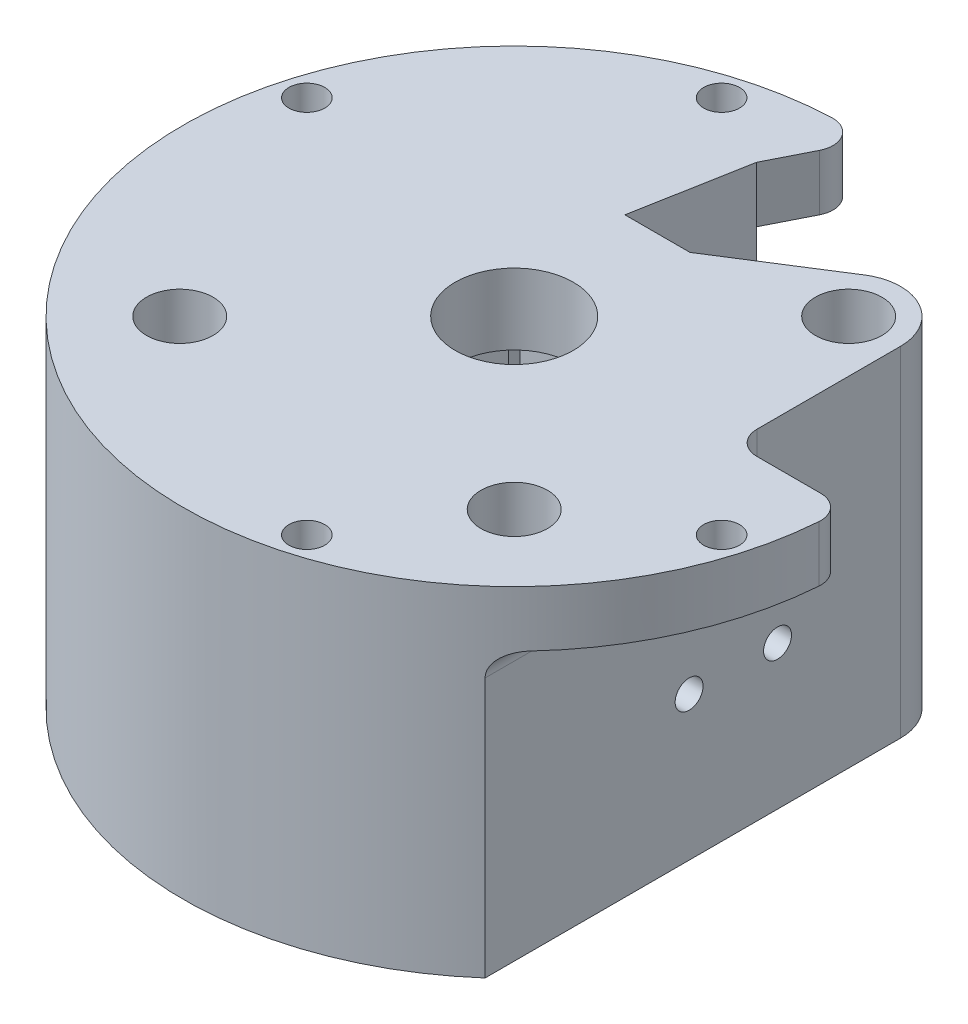
SolidWorks part; units mm, degrees
ref_plane "Front Plane" through (0, 0, 0) normal (0, 0, 1) x (1, 0, 0)
ref_plane "Top Plane" through (0, 0, 0) normal (0, 1, 0) x (1, 0, 0)
ref_plane "Right Plane" through (0, 0, 0) normal (1, 0, 0) x (0, 0, -1)
sketch "Sketch2" plane through (0, 0, 0) normal (0, 1, 0) x (1, 0, 0)
  line L0 (-46.3406, 15.0473) -> (-20.9548, -39.0545) construction
  line L1 (-17.9605, 17.9605) -> (-3.0236, 17.9605) construction
  line L2 (-17.9605, 17.9605) -> (-17.9605, -17.9605) construction
  line L3 (-17.9605, -17.9605) -> (17.9605, -17.9605) construction
  line L4 (17.9605, 17.9605) -> (17.9605, -17.9605) construction
  line L5 (-17.9605, 17.9605) -> (17.9605, -17.9605) construction
  line L6 (-17.9605, -17.9605) -> (17.9605, 17.9605) construction
  line L7 (10.05, -30.05) -> (-10.05, -30.05)
  line L8 (10.05, -30.05) -> (10.05, 10.05)
  line L9 (10.05, 10.05) -> (3.4925, 10.05)
  line L10 (-10.05, -30.05) -> (-10.05, 10.05)
  line L11 (10.05, -30.05) -> (-10.05, 10.05) construction
  line L12 (10.05, 10.05) -> (-10.05, -30.05) construction
  line L13 (-3.4925, 15.384) -> (3.4925, 15.384) construction
  line L14 (-3.4925, 15.384) -> (-3.4925, 10.05)
  line L15 (0, 10.05) -> (3.4925, 10.05) construction
  line L16 (3.4925, 15.384) -> (3.4925, 10.05)
  line L17 (0, 12.717) -> (3.4925, 10.05) construction
  line L18 (0, 12.717) -> (3.4925, 15.384) construction
  line L19 (-1.3182, 27.3309) -> (-10.8398, 32.142)
  line L20 (-1.3182, 27.3309) -> (-23.3118, -16.1961) construction
  line L21 (-23.3118, -16.1961) -> (-32.8333, -11.3851) construction
  line L22 (-10.8398, 32.142) -> (-32.8333, -11.3851) construction
  line L23 (-1.3182, 27.3309) -> (-32.8333, -11.3851) construction
  line L24 (-23.3118, -16.1961) -> (-10.8398, 32.142) construction
  line L25 (23.5324, -17.9605) -> (23.5324, -26.6597)
  line L26 (23.5324, -17.9605) -> (23.5324, 17.9605)
  line L27 (3.4925, 15.384) -> (14.9767, 22.6661)
  line L28 (-10.8398, 32.142) -> (-12.8493, 33.1573)
  line L29 (-3.4925, 15.384) -> (-1.3182, 27.3309)
  line L30 (-3.0236, 17.9605) -> (7.5558, 17.9605) construction
  line L31 (7.5558, 17.9605) -> (17.9605, 17.9605) construction
  line L32 (-3.4925, 15.384) -> (0, 12.717) construction
  line L33 (-3.4925, 10.05) -> (0, 12.717) construction
  line L34 (0, 10.05) -> (-3.4925, 10.05) construction
  line L35 (-3.4925, 10.05) -> (-10.05, 10.05)
  line L36 (-3.4925, 10.05) -> (0, 10.05) construction
  line L37 (3.4925, 10.05) -> (0, 10.05) construction
  arc A0 (-12.8493, 33.1573) -> (23.5324, -26.6597) centre (0, 0) ccw
  circle A1 centre (-17.9605, 17.9605) radius 3.5719 construction
  circle A2 centre (17.9605, 17.9605) radius 3.5719
  circle A3 centre (17.9605, -17.9605) radius 3.5719
  circle A4 centre (-17.9605, -17.9605) radius 3.5719
  arc A5 (-4.4901, 4.4901) -> (4.4901, 4.4901) centre (0, 0) ccw construction
  arc A6 (-7.1064, 7.1064) -> (7.1064, 7.1064) centre (0, 0) ccw construction
  circle A7 centre (-17.9605, -17.9605) radius 5.5719 construction
  arc A8 (23.5324, -17.9605) -> (17.9605, -12.3886) centre (17.9605, -17.9605) ccw construction
  arc A9 (23.5324, 17.9605) -> (14.9767, 22.6661) centre (17.9605, 17.9605) ccw
  arc A10 (23.5324, -26.6597) -> (-12.8493, 33.1573) centre (0, 0) ccw construction
  arc A11 (0, 10.05) -> (-7.1064, 7.1064) centre (0, 0) ccw construction
  arc A12 (4.4901, 4.4901) -> (-4.4901, 4.4901) centre (0, 0) ccw construction
  arc A13 (7.1064, 7.1064) -> (0, 10.05) centre (0, 0) ccw construction
  arc A14 (14.0206, 14.0206) -> (17.9605, 12.3886) centre (17.9605, 17.9605) ccw construction
  arc A15 (12.3886, 17.9605) -> (14.0206, 14.0206) centre (17.9605, 17.9605) ccw construction
  arc A16 (14.9767, 22.6661) -> (12.3886, 17.9605) centre (17.9605, 17.9605) ccw construction
  arc A17 (17.9605, 12.3886) -> (23.5324, 17.9605) centre (17.9605, 17.9605) ccw construction
  arc A18 (12.3886, -17.9605) -> (23.5324, -17.9605) centre (17.9605, -17.9605) ccw construction
  arc A19 (14.0206, -14.0206) -> (12.3886, -17.9605) centre (17.9605, -17.9605) ccw construction
  arc A20 (17.9605, -12.3886) -> (14.0206, -14.0206) centre (17.9605, -17.9605) ccw construction
  point P12 (0, -10)
  point P17 (0, 12.717)
  point P23 (-17.0758, 7.9729)
  point P35 (-32.1922, -15.1054)
  dimension "D1" = 71.12
  dimension "D3" = 7.1437
  dimension "D4" = 12.7
  dimension "D2" = 50.8
  dimension "D5" = 20.1
  dimension "D6" = 40.1
  dimension "D7" = 10
  dimension "D8" = 6.985
  dimension "D9" = 5.334
  dimension "D10" = 10.668
  dimension "D11" = 48.768
  dimension "D12" = 10.668
  dimension "D13" = 2
  dimension "D14" = 1
  dimension "D15" = 38.056
extrude "Boss-Extrude1" add sketch "Sketch2" along normal blind 1.905
sketch "Sketch3" plane through (0, 1.905, 0) normal (0, 1, 0) x (1, 0, 0)
  line L0 (-1.3182, 27.3309) -> (-23.3118, -16.1961) construction
  line L1 (-10.8398, 32.142) -> (-32.8333, -11.3851) construction
  line L2 (-23.3118, -16.1961) -> (-32.8333, -11.3851) construction
  line L3 (-10.8398, 32.142) -> (-32.8333, -11.3851)
  line L4 (-1.3182, 27.3309) -> (-9.7636, 10.6168)
  line L5 (-23.3118, -16.1961) -> (-32.8333, -11.3851)
  line L6 (-10.05, 10.05) -> (-9.415, 10.05) construction
  line L7 (-9.7636, 10.6168) -> (-10.05, 10.05) construction
  line L8 (-10.3364, 9.4832) -> (-23.3118, -16.1961)
  line L9 (-10.05, 10.05) -> (-10.3364, 9.4832) construction
  line L10 (-10.05, 9.415) -> (-10.05, 10.05) construction
  line L11 (-10.05, 10.05) -> (-3.4925, 10.05)
  line L12 (-3.4925, 10.05) -> (-3.4925, 15.384)
  line L13 (-3.4925, 15.384) -> (-1.3182, 27.3309)
  line L14 (-1.3182, 27.3309) -> (-12.8493, 33.1573)
  line L15 (23.5324, -26.6597) -> (23.5324, 17.9605)
  line L16 (14.9767, 22.6661) -> (3.4925, 15.384)
  line L17 (3.4925, 15.384) -> (3.4925, 10.05)
  line L18 (3.4925, 10.05) -> (10.05, 10.05)
  line L19 (10.05, 10.05) -> (10.05, -30.05)
  line L20 (10.05, -30.05) -> (-10.05, -30.05)
  line L21 (-10.05, -30.05) -> (-10.05, 10.05)
  line L22 (-9.415, 10.05) -> (-3.4925, 10.05)
  line L23 (-3.4925, 10.05) -> (-3.4925, 15.384)
  line L24 (-3.4925, 15.384) -> (-1.3182, 27.3309)
  line L25 (-10.8398, 32.142) -> (-12.8493, 33.1573)
  line L26 (23.5324, -26.6597) -> (23.5324, 17.9605)
  line L27 (14.9767, 22.6661) -> (3.4925, 15.384)
  line L28 (3.4925, 15.384) -> (3.4925, 10.05)
  line L29 (3.4925, 10.05) -> (10.05, 10.05)
  line L30 (10.05, 10.05) -> (10.05, -30.05)
  line L31 (10.05, -30.05) -> (-10.05, -30.05)
  line L32 (-10.05, -30.05) -> (-10.05, 9.415)
  line L33 (-1.3182, 27.3309) -> (-10.8398, 32.142) construction
  arc A0 (-10.3364, 9.4832) -> (-10.05, 9.415) centre (-10.05, 10.05) ccw
  circle A1 centre (17.9605, 17.9605) radius 3.5719 construction
  circle A2 centre (17.9605, -17.9605) radius 3.5719 construction
  arc A3 (-12.8493, 33.1573) -> (23.5324, -26.6597) centre (0, 0) ccw
  arc A4 (23.5324, 17.9605) -> (14.9767, 22.6661) centre (17.9605, 17.9605) ccw
  arc A5 (-12.8493, 33.1573) -> (23.5324, -26.6597) centre (0, 0) ccw
  arc A6 (23.5324, 17.9605) -> (14.9767, 22.6661) centre (17.9605, 17.9605) ccw
  circle A7 centre (-17.9605, -17.9605) radius 3.5719 construction
  circle A8 centre (17.9605, 17.9605) radius 3.5719
  circle A9 centre (17.9605, -17.9605) radius 3.5719
  circle A10 centre (-17.9605, -17.9605) radius 3.5719
  arc A11 (-9.7636, 10.6168) -> (-10.3364, 9.4832) centre (-10.05, 10.05) ccw construction
  arc A12 (-10.05, 9.415) -> (-9.415, 10.05) centre (-10.05, 10.05) ccw construction
  arc A13 (-9.415, 10.05) -> (-9.7636, 10.6168) centre (-10.05, 10.05) ccw
  dimension "D1" = 1.27
  dimension "D2" = 0
extrude "Boss-Extrude2" add sketch "Sketch3" along normal blind 19.558
sketch "Sketch4" plane through (0, 21.463, 0) normal (0, 1, 0) x (1, 0, 0)
  line L0 (0, 10.05) -> (3.4925, 10.05) construction
  line L1 (-3.4925, 15.384) -> (3.4925, 15.384) construction
  line L2 (0, 10.05) -> (-3.4925, 10.05) construction
  line L3 (0, 10.05) -> (-3.4925, 10.05)
  line L4 (0, 10.05) -> (3.4925, 10.05)
  line L5 (-3.4925, 15.384) -> (3.4925, 15.384)
  line L6 (-23.3118, -16.1961) -> (-32.8333, -11.3851) construction
  line L7 (-10.8398, 32.142) -> (-32.8333, -11.3851) construction
  line L8 (-1.3182, 27.3309) -> (-23.3118, -16.1961) construction
  line L9 (-23.3118, -16.1961) -> (-32.8333, -11.3851)
  line L10 (-10.8398, 32.142) -> (-32.8333, -11.3851)
  line L11 (-10.05, 10.05) -> (-3.4925, 10.05)
  line L12 (-10.05, -30.05) -> (-10.05, 10.05)
  line L13 (10.05, -30.05) -> (-10.05, -30.05)
  line L14 (10.05, 10.05) -> (10.05, -30.05)
  line L15 (3.4925, 10.05) -> (10.05, 10.05)
  line L16 (3.4925, 15.384) -> (3.4925, 10.05)
  line L17 (14.9767, 22.6661) -> (3.4925, 15.384)
  line L18 (23.5324, -26.6597) -> (23.5324, 17.9605)
  line L19 (-1.3182, 27.3309) -> (-12.8493, 33.1573)
  line L20 (-3.4925, 15.384) -> (-1.3182, 27.3309)
  line L21 (-3.4925, 10.05) -> (-3.4925, 15.384)
  line L22 (-9.415, 10.05) -> (-3.4925, 10.05)
  line L23 (-10.05, -30.05) -> (-10.05, 9.415)
  line L24 (10.05, -30.05) -> (-10.05, -30.05)
  line L25 (10.05, 10.05) -> (10.05, -30.05)
  line L26 (3.4925, 10.05) -> (10.05, 10.05)
  line L27 (3.4925, 15.384) -> (3.4925, 10.05) construction
  line L28 (14.9767, 22.6661) -> (3.4925, 15.384)
  line L29 (23.5324, -26.6597) -> (23.5324, 17.9605)
  line L30 (-10.8398, 32.142) -> (-12.8493, 33.1573)
  line L31 (-3.4925, 15.384) -> (-1.3182, 27.3309)
  line L32 (-3.4925, 10.05) -> (-3.4925, 15.384) construction
  line L33 (-1.3182, 27.3309) -> (-9.7636, 10.6168)
  line L34 (-1.3182, 27.3309) -> (-10.8398, 32.142) construction
  line L35 (-10.05, 10.05) -> (-10.3364, 9.4832) construction
  line L36 (-10.3364, 9.4832) -> (-23.3118, -16.1961)
  line L37 (-10.05, 9.415) -> (-10.05, 10.05) construction
  line L38 (-10.05, 10.05) -> (-9.415, 10.05) construction
  line L39 (-9.7636, 10.6168) -> (-10.05, 10.05) construction
  circle A0 centre (17.9605, 17.9605) radius 3.5719 construction
  circle A1 centre (17.9605, -17.9605) radius 3.5719 construction
  arc A2 (23.5324, 17.9605) -> (14.9767, 22.6661) centre (17.9605, 17.9605) ccw
  arc A3 (-12.8493, 33.1573) -> (23.5324, -26.6597) centre (0, 0) ccw
  arc A4 (23.5324, 17.9605) -> (14.9767, 22.6661) centre (17.9605, 17.9605) ccw
  arc A5 (-12.8493, 33.1573) -> (23.5324, -26.6597) centre (0, 0) ccw
  circle A6 centre (-17.9605, -17.9605) radius 3.5719 construction
  circle A7 centre (17.9605, 17.9605) radius 3.5719
  circle A8 centre (17.9605, -17.9605) radius 3.5719
  circle A9 centre (-17.9605, -17.9605) radius 3.5719
  arc A10 (-9.415, 10.05) -> (-9.7636, 10.6168) centre (-10.05, 10.05) ccw construction
  arc A11 (-10.3364, 9.4832) -> (-10.05, 9.415) centre (-10.05, 10.05) ccw construction
  arc A12 (-9.415, 10.05) -> (-9.7636, 10.6168) centre (-10.05, 10.05) ccw
  arc A13 (-10.3364, 9.4832) -> (-10.05, 9.415) centre (-10.05, 10.05) ccw
  dimension "D1" = 0
extrude "Boss-Extrude3" add sketch "Sketch4" along normal blind 7.366
sketch "Sketch5" plane through (0, 28.829, 0) normal (0, 1, 0) x (1, 0, 0)
  line L0 (3.4925, 15.384) -> (-3.4925, 15.384) construction
  line L1 (3.4925, 15.384) -> (-3.4925, 15.384)
  line L11 (-10.05, 10.05) -> (-3.4925, 10.05)
  line L12 (-10.05, -30.05) -> (-10.05, 10.05)
  line L13 (10.05, -30.05) -> (-10.05, -30.05)
  line L14 (10.05, 10.05) -> (10.05, -30.05)
  line L15 (3.4925, 10.05) -> (10.05, 10.05)
  line L16 (3.4925, 15.384) -> (3.4925, 10.05)
  line L17 (14.9767, 22.6661) -> (3.4925, 15.384)
  line L18 (23.5324, -26.6597) -> (23.5324, 17.9605)
  line L19 (-1.3182, 27.3309) -> (-12.8493, 33.1573)
  line L20 (-3.4925, 15.384) -> (-1.3182, 27.3309)
  line L21 (-3.4925, 10.05) -> (-3.4925, 15.384)
  line L22 (-10.05, 10.05) -> (-3.4925, 10.05) construction
  line L23 (-10.05, -30.05) -> (-10.05, 10.05) construction
  line L24 (10.05, -30.05) -> (-10.05, -30.05) construction
  line L25 (10.05, 10.05) -> (10.05, -30.05) construction
  line L26 (3.4925, 10.05) -> (10.05, 10.05) construction
  line L27 (3.4925, 15.384) -> (3.4925, 10.05) construction
  line L28 (14.9767, 22.6661) -> (3.4925, 15.384)
  line L29 (23.5324, -26.6597) -> (23.5324, 17.9605)
  line L30 (-1.3182, 27.3309) -> (-12.8493, 33.1573)
  line L31 (-3.4925, 15.384) -> (-1.3182, 27.3309)
  line L32 (-3.4925, 10.05) -> (-3.4925, 15.384) construction
  circle A0 centre (17.9605, 17.9605) radius 3.5719 construction
  circle A1 centre (17.9605, -17.9605) radius 3.5719 construction
  arc A2 (23.5324, 17.9605) -> (14.9767, 22.6661) centre (17.9605, 17.9605) ccw
  arc A3 (-12.8493, 33.1573) -> (23.5324, -26.6597) centre (0, 0) ccw
  arc A4 (23.5324, 17.9605) -> (14.9767, 22.6661) centre (17.9605, 17.9605) ccw
  arc A5 (-12.8493, 33.1573) -> (23.5324, -26.6597) centre (0, 0) ccw
  circle A6 centre (-17.9605, -17.9605) radius 3.5719 construction
  circle A7 centre (17.9605, 17.9605) radius 3.5719
  circle A8 centre (17.9605, -17.9605) radius 3.5719
  circle A9 centre (-17.9605, -17.9605) radius 3.5719
  arc A10 (4.4901, 4.4901) -> (-4.4901, 4.4901) centre (0, 0) ccw construction
  arc A11 (-4.4901, 4.4901) -> (4.4901, 4.4901) centre (0, 0) ccw construction
  arc A12 (4.4901, 4.4901) -> (-4.4901, 4.4901) centre (0, 0) ccw
  arc A13 (-4.4901, 4.4901) -> (4.4901, 4.4901) centre (0, 0) ccw
  dimension "D1" = 0
extrude "Boss-Extrude4" add sketch "Sketch5" along normal blind 7.62
sketch "Sketch8" plane through (0, 36.449, 0) normal (0, 1, 0) x (1, 0, 0)
  line L0 (-1.3182, 27.3309) -> (-12.8493, 33.1573)
  line L1 (-1.3182, 27.3309) -> (2.7846, 35.4508)
  line L2 (23.5324, 0) -> (35.56, 0)
  line L3 (23.5324, -17.9605) -> (23.5324, 17.9605) construction
  line L4 (23.5324, -17.9605) -> (23.5324, 0)
  line L5 (23.5324, -17.9605) -> (23.5324, -26.6597) construction
  line L6 (23.5324, -17.9605) -> (23.5324, -26.6597)
  arc A0 (23.5324, -26.6597) -> (-12.8493, 33.1573) centre (0, 0) ccw construction
  arc A1 (23.5324, -26.6597) -> (35.56, 0) centre (0, 0) ccw
  arc A2 (35.56, 0) -> (2.7846, 35.4508) centre (0, 0) ccw construction
  arc A3 (2.7846, 35.4508) -> (-12.8493, 33.1573) centre (0, 0) ccw
extrude "Boss-Extrude5" add sketch "Sketch8" against normal blind 6
sketch "Sketch7" plane through (0, 36.449, 0) normal (0, 1, 0) x (1, 0, 0)
  line L0 (-31.4663, 9.1924) -> (-9.1924, 31.4663) construction
  line L1 (-9.1924, 31.4663) -> (31.4663, -9.1924) construction
  line L2 (31.4663, -9.1924) -> (9.1924, -31.4663) construction
  line L3 (9.1924, -31.4663) -> (-31.4663, 9.1924) construction
  line L4 (-17.9605, -17.9605) -> (17.9605, 17.9605) construction
  line L5 (-31.4663, 9.1924) -> (31.4663, -9.1924) construction
  line L6 (9.1924, -31.4663) -> (-9.1924, 31.4663) construction
  circle A0 centre (-31.4663, 9.1924) radius 1.925
  circle A1 centre (-9.1924, 31.4663) radius 1.925
  circle A2 centre (31.4663, -9.1924) radius 1.925
  circle A3 centre (9.1924, -31.4663) radius 1.925
  point P6 (0, 0)
  dimension "D3" = 3.85
  dimension "D1" = 57.5
  dimension "D2" = 31.5
extrude "Cut-Extrude2" cut sketch "Sketch7" against normal blind 5.75
sketch "Sketch6" plane through (23.5324, 0, 0) normal (1, 0, 0) x (0, 0, -1)
  line L1 (-4.75, 15.449) -> (4.75, 15.449) construction
  line L5 (0, 30.449) -> (-26.6597, 30.449) construction
  line L6 (0, 30.449) -> (-26.6597, 30.449) construction
  circle A0 centre (-4.75, 15.449) radius 1.5
  circle A1 centre (4.75, 15.449) radius 1.5
  point P3 (0, 15.449)
  dimension "D3" = 15
  dimension "D1" = 3
  dimension "D2" = 9.5
fillet "Fillet1" radius 2.54 8 edges at (23.5324, 30.449, 13.3299) (0, 21.463, -10.05) (0, 21.463, -15.384) (2.7846, 33.449, -35.4508) (-12.8493, 15.2245, -33.1573) (3.4925, 0, -12.717) (35.56, 33.449, 0) (23.5324, 33.449, 0)
extrude "Cut-Extrude3" cut sketch "Sketch6" against normal blind 4
equation "\"AIRFRAME_OD\"= 3.142in"
equation "\"AIRFRAME_ID\"= 3.00in"
equation "\"FLAT_T\"= 0.125in"
equation "\"NOSE_EXP_L\"= 3.5in"
equation "\"NOSE_SHOULDER_L\"= 1.5in"
equation "\"MAIN_L\"= 30in"
equation "\"RECO_COUP_L\"= 6in"
equation "\"RECO_SWITCH_L\"= 1.5in"
equation "\"DROGUE_L\"= 14in"
equation "\"ATS_FORE_COUP_L\"= 4in"
equation "\"ATS_AFT_COUP_L\"= 2.5in"
equation "\"LOWER_L\"= 16in"
equation "\"FIN_N\"= 4"
equation "\"CR_AFT_X\"= 0.5in"
equation "\"CR_FORE_X\"= 6in"
equation "\"COUPLER_OD\"= 2.998in"
equation "\"COUPLER_ID\"= 2.875in"
equation "\"RECO_ROD_X\"= 1.5in"
equation "\"ATS_ROD_X\"= 2in"
equation "\"FIN_ROOT\"= 5in"
equation "\"FIN_X\"= 0.75in"
equation "\"MOTOR_OD\"= 2.25in"
equation "\"MOTOR_ID\"= 2.126in"
equation "\"MOTOR_L\"= 8in"
equation "\"MOTOR_LOWER_X\"= 0.5in"
equation "\"NOSE_CONE_L\"=14.5in"
equation "\"ATS_LIPO_L\" = 1.92in"
equation "\"ATS_LIPO_W\" = 0.42in"
equation "\"ATS_LIPO_H\" = 0.94in "
equation "\"ATS_STANDOFF_H\" = 10mm"
equation "\"ATS_STANDOFF_OD\" = 5.2mm"
equation "\"ATS_PCB_L\" = 2.5in"
equation "\"ATS_PCB_W\" = 1.45in"
equation "\"ATS_PCB_H\" = 1.2in"
equation "\"ATS_PCB_HOLESEP_W\" = 1.33in - 0.0985in"
equation "\"ATS_ALTI_L\" = 1.05in"
equation "\"ATS_ALTI_W\" = 0.7in"
equation "\"ATS_ALTI_H\" = 0.4in"
equation "\"D11@Sketch2\"=\"ATS_LIPO_L\""
equation "\"D12@Sketch2\"=\"ATS_LIPO_W\""
equation "\"D1@Boss-Extrude2\"=\"ATS_LIPO_H\""
